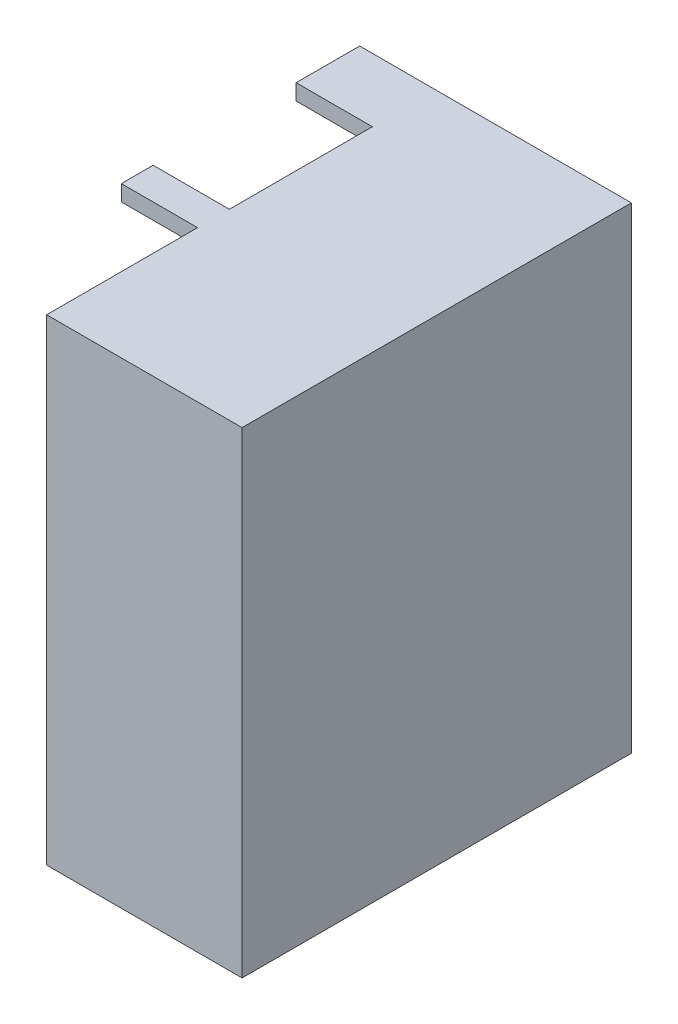
SolidWorks part; units mm, degrees
ref_plane "Front Plane" through (0, 0, 0) normal (0, 0, 1) x (1, 0, 0)
ref_plane "Top Plane" through (0, 0, 0) normal (0, 1, 0) x (1, 0, 0)
ref_plane "Right Plane" through (0, 0, 0) normal (1, 0, 0) x (0, 0, -1)
sketch "Sketch1" plane through (0, 0, 0) normal (0, 1, 0) x (1, 0, 0)
  line L3 (0, 0) -> (2.4, 0)
  line L4 (0, 0) -> (0, -2)
  line L5 (0, -2) -> (2.4, -2)
  line L6 (2.4, 0) -> (2.4, -2)
  line L7 (0, -6.5) -> (2.4, -6.5)
  line L8 (0, -6.5) -> (0, -7.5)
  line L9 (0, -7.5) -> (2.4, -7.5)
  line L10 (2.4, -6.5) -> (2.4, -7.5)
  line L11 (2.4, 0) -> (8.55, 0)
  line L12 (2.4, 0) -> (2.4, -12.25)
  line L13 (2.4, -12.25) -> (8.55, -12.25)
  line L14 (8.55, 0) -> (8.55, -12.25)
  point P8 (0, -1)
  point P10 (0, -7)
  dimension "D1" = 2
  dimension "D2" = 1
  dimension "D3" = 6
  dimension "D4" = 2.4
  dimension "D5" = 6.15
  dimension "D6" = 12.25
extrude "Boss-Extrude1" add sketch "Sketch1" along normal blind 14 contours L14 L11 L6 L12 L10 L13 region at (5.475, 0, 6.125)
extrude "Boss-Extrude2" add sketch "Sketch1<3>" against normal blind 0.5 contours L10 L7 L8 L9 | L6 L3 L4 L5 | L14 L11 L6 L12 L10 L13 region at (1.2, 0, 1) region at (5.475, 0, 6.125) region at (1.2, 0, 7)
sketch "Sketch1<3>" plane through (0, 0, 0) normal (0, 1, 0) x (1, 0, 0) same geometry as "Sketch1"
extrude "Boss-Extrude3" add sketch "Sketch1<4>" along normal blind 0.5 from surface contours L6 L3 L4 L5 | L10 L7 L8 L9 | L14 L11 L6 L12 L10 L13 region at (1.2, 0, 1) region at (5.475, 0, 6.125) region at (1.2, 0, 7) starting at face at (5.475, 14, 6.125)
sketch "Sketch1<4>" plane through (0, 0, 0) normal (0, 1, 0) x (1, 0, 0) same geometry as "Sketch1"
